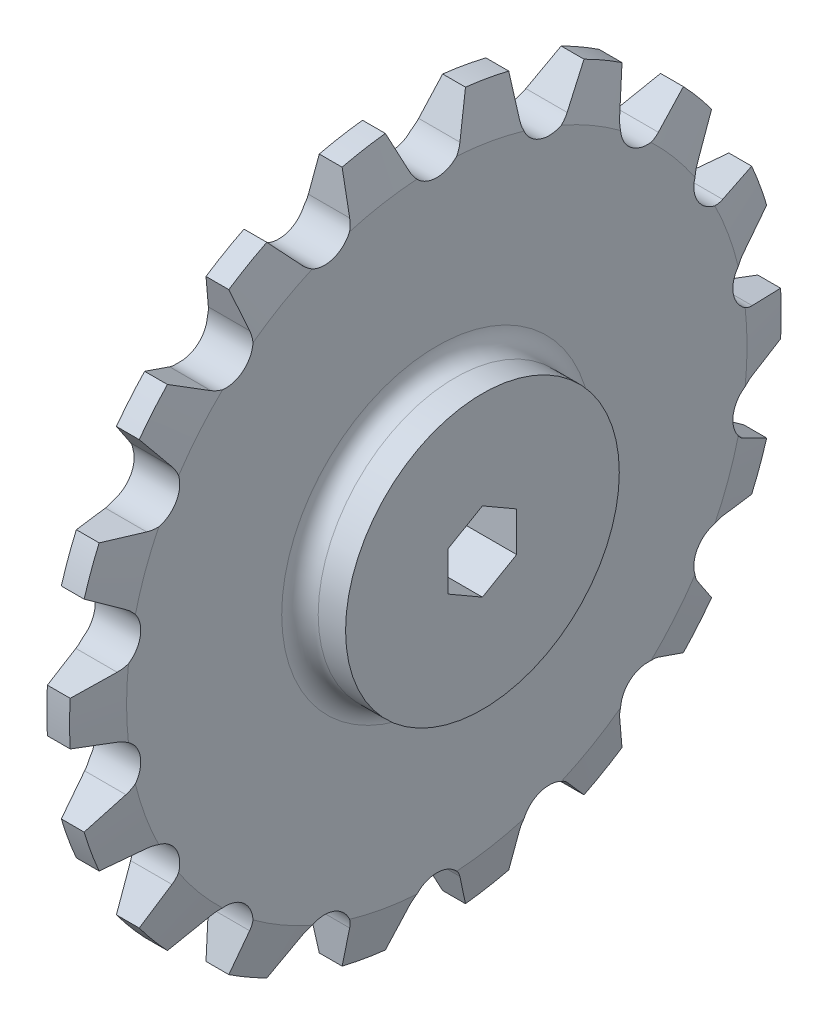
SolidWorks part; units mm, degrees
ref_plane "Front Plane" through (0, 0, 0) normal (0, 0, 1) x (1, 0, 0)
ref_plane "Top Plane" through (0, 0, 0) normal (0, 1, 0) x (1, 0, 0)
ref_plane "Right Plane" through (0, 0, 0) normal (1, 0, 0) x (0, 0, -1)
sketch "Sketch1" plane through (0, 0, 0) normal (0, 1, 0) x (1, 0, 0)
  line L0 (-6.35, 43.18) -> (-4.7625, 49.53)
  line L1 (0, 0) -> (-6.35, 0)
  line L2 (0, 0) -> (0, 43.18)
  line L3 (0, 43.18) -> (-6.35, 43.18)
  line L4 (-6.35, 0) -> (-6.35, 43.18)
  line L5 (-4.7625, 49.53) -> (-1.5875, 49.53)
  line L6 (-1.5875, 49.53) -> (0, 43.18)
  line L8 (-19.05, 0) -> (6.35, 0)
  line L9 (-19.05, 0) -> (-19.05, 19.05)
  line L10 (-19.05, 19.05) -> (6.35, 19.05)
  line L11 (6.35, 0) -> (6.35, 19.05)
  point P7 (-3.175, 49.53)
  point P8 (-3.175, 43.18)
  dimension "D1" = 3.175
  dimension "D2" = 6.35
  dimension "D3" = 6.35
  dimension "D4" = 43.18
  dimension "D5" = 19.05
  dimension "D6" = 6.35
  dimension "D7" = 12.7
revolve "Revolve1" add sketch "Sketch1" angle 360 about L8 region at (-3.175, 0, -46.0022) region at (-3.175, 0, -31.115) region at (-3.175, 0, -9.525) region at (-12.7, 0, -9.525) region at (3.175, 0, -9.525)
sketch "Sketch2" plane through (0, 0, 0) normal (1, 0, 0) x (0, 0, -1)
  line L0 (15.6338, 42.9536) -> (0, 45.7102) construction
  line L1 (0, 45.7102) -> (-15.6338, 42.9536) construction
  line L2 (-15.6338, 42.9536) -> (-29.382, 35.0161) construction
  line L3 (-29.382, 35.0161) -> (-39.5862, 22.8551) construction
  line L4 (-39.5862, 22.8551) -> (-45.0158, 7.9375) construction
  line L5 (-45.0158, 7.9375) -> (-45.0158, -7.9375) construction
  line L6 (-45.0158, -7.9375) -> (-39.5862, -22.8551) construction
  line L7 (-39.5862, -22.8551) -> (-29.382, -35.0161) construction
  line L8 (-29.382, -35.0161) -> (-15.6338, -42.9536) construction
  line L9 (-15.6338, -42.9536) -> (0, -45.7102) construction
  line L10 (0, -45.7102) -> (15.6338, -42.9536) construction
  line L11 (15.6338, -42.9536) -> (29.382, -35.0161) construction
  line L12 (29.382, -35.0161) -> (39.5862, -22.8551) construction
  line L13 (39.5862, -22.8551) -> (45.0158, -7.9375) construction
  line L14 (45.0158, -7.9375) -> (45.0158, 7.9375) construction
  line L15 (45.0158, 7.9375) -> (39.5862, 22.8551) construction
  line L16 (39.5862, 22.8551) -> (29.382, 35.0161) construction
  line L17 (29.382, 35.0161) -> (15.6338, 42.9536) construction
  line L18 (-3.52, 44.2522) -> (-7.9818, 55.024)
  line L19 (0, 0) -> (0, 45.7102) construction
  line L20 (3.52, 44.2522) -> (7.9818, 55.024)
  line L21 (-7.9818, 55.024) -> (7.9818, 55.024)
  circle A0 centre (0, 0) radius 45.0158 construction
  circle A1 centre (0, 45.7102) radius 3.81
  dimension "D2" = 7.62
  dimension "D1" = 15.875
  dimension "D3" = 22.5
extrude "Cut-Extrude1" cut sketch "Sketch2" against normal through all both contours A1 L20 L21 L18 | A1 L20 region at (0, 51.7356, 0) region at (0, 45.7102, 0)
pattern_circular "CirPattern1" count 18 over 360 about axis through (6.35, 0, 0) along (-1, 0, 0) of "Cut-Extrude1"
sketch "Sketch3" plane through (-19.05, 0, 0) normal (-1, 0, 0) x (0, 0, 1)
  line L1 (0, 5.4993) -> (-4.7625, 2.7496)
  line L2 (-4.7625, 2.7496) -> (-4.7625, -2.7496)
  line L3 (-4.7625, -2.7496) -> (0, -5.4993)
  line L4 (0, -5.4993) -> (4.7625, -2.7496)
  line L5 (4.7625, -2.7496) -> (4.7625, 2.7496)
  line L6 (4.7625, 2.7496) -> (0, 5.4993)
  circle A0 centre (0, 0) radius 4.7625 construction
  dimension "D1" = 9.525
extrude "Cut-Extrude2" cut sketch "Sketch3" against normal through all both
fillet "Fillet1" radius 2.54 2 edges at (0, 0, 19.05) (-6.35, 0, 19.05)
